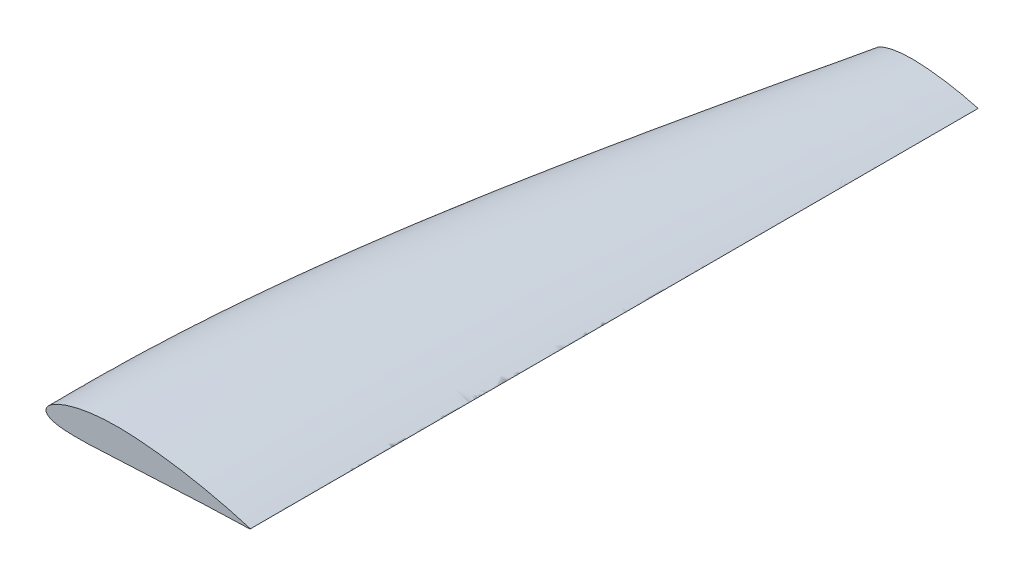
SolidWorks part; units mm, degrees
ref_plane "Front Plane" through (0, 0, 0) normal (1, 0, 0) x (0, 1, 0)
ref_plane "Top Plane" through (0, 0, 0) normal (0, 0, 1) x (0, 1, 0)
ref_plane "Right Plane" through (0, 0, 0) normal (0, 1, 0) x (-1, 0, 0)
curve "Curve1"
  spline degree 3 poles (140.0272, 0.204, 0) (139.9568, 0.2252, 0) (139.6757, 0.3101, 0) (139.0445, 0.4996, 0) (137.9962, 0.8116, 0) (136.5364, 1.24, 0) (134.6729, 1.777, 0) (132.4156, 2.4129, 0) (129.7768, 3.1359, 0) (126.7711, 3.9337, 0) (123.4152, 4.7928, 0) (119.7281, 5.6984, 0) (115.7307, 6.6363, 0) (111.4464, 7.5912, 0) (106.9, 8.5481, 0) (102.1186, 9.4924, 0) (97.1306, 10.4094, 0) (91.9664, 11.285, 0) (86.6574, 12.105, 0) (81.2364, 12.857, 0) (75.7371, 13.5278, 0) (70.1942, 14.1063, 0) (64.643, 14.582, 0) (59.1045, 14.945, 0) (53.595, 15.1934, 0) (48.1487, 15.2539, 0) (42.8195, 15.1314, 0) (37.6645, 14.8278, 0) (32.721, 14.3506, 0) (28.0244, 13.7113, 0) (23.608, 12.9241, 0) (19.5026, 12.0063, 0) (15.7359, 10.9777, 0) (12.3325, 9.8591, 0) (9.3132, 8.6734, 0) (6.6949, 7.4424, 0) (4.4906, 6.1877, 0) (2.7084, 4.928, 0) (1.3523, 3.6768, 0) (0.4223, 2.4391, 0) (-0.0704, 1.2019, 0) (-0.0774, -0.0155, 0) (0.3962, -1.1349, 0) (1.3132, -2.0898, 0) (2.6166, -2.8909, 0) (4.297, -3.5632, 0) (6.348, -4.1161, 0) (8.7591, -4.5545, 0) (11.516, -4.8827, 0) (14.6016, -5.1058, 0) (17.9973, -5.2305, 0) (21.6831, -5.2648, 0) (25.6381, -5.2189, 0) (29.8408, -5.1042, 0) (34.2692, -4.9332, 0) (38.9005, -4.7202, 0) (43.7112, -4.4799, 0) (48.6771, -4.2275, 0) (53.7919, -3.9752, 0) (59.0436, -3.7443, 0) (64.3998, -3.4808, 0) (69.8109, -3.2013, 0) (75.2301, -2.9143, 0) (80.6252, -2.6276, 0) (85.9637, -2.348, 0) (91.213, -2.0804, 0) (96.3409, -1.8293, 0) (101.3154, -1.5967, 0) (106.1052, -1.3844, 0) (110.68, -1.1929, 0) (115.0103, -1.0216, 0) (119.0681, -0.87, 0) (122.827, -0.7367, 0) (126.2621, -0.6209, 0) (129.3505, -0.521, 0) (132.0713, -0.4363, 0) (134.4061, -0.3656, 0) (136.3389, -0.3086, 0) (137.8565, -0.2644, 0) (138.948, -0.2331, 0) (139.6061, -0.2145, 0) (139.8994, -0.2061, 0) (139.9728, -0.204, 0) knots 0 0 0 0 0.000765 0.003057 0.00686 0.012149 0.018893 0.027046 0.036559 0.047372 0.059416 0.072616 0.086892 0.102153 0.118305 0.13525 0.152883 0.171093 0.18977 0.208797 0.228058 0.247433 0.266803 0.286048 0.305204 0.324202 0.342731 0.360679 0.377941 0.394414 0.410004 0.424621 0.438187 0.450631 0.461894 0.471932 0.480721 0.488263 0.494602 0.499855 0.504257 0.508229 0.5122 0.516589 0.52179 0.528018 0.535367 0.543866 0.553506 0.564253 0.57606 0.588869 0.602615 0.617228 0.632631 0.648744 0.665486 0.682768 0.700501 0.71879 0.737484 0.756321 0.775188 0.793972 0.812558 0.830833 0.848683 0.865998 0.882668 0.898589 0.913658 0.927778 0.940857 0.952809 0.963554 0.97302 0.981143 0.987868 0.993148 0.996946 0.999235 1 1 1 1
curve "Curve2"
  spline degree 3 poles (70, 0.091, 0) (68.8345, 0.4083, 0) (66.5092, 1.0413, 0) (61.851, 2.1922, 0) (56.0257, 3.4639, 0) (49.0189, 4.7174, 0) (42.0176, 5.745, 0) (35.0124, 6.4779, 0) (28.0078, 6.935, 0) (22.1603, 6.9396, 0) (17.4914, 6.6166, 0) (13.9849, 6.1912, 0) (10.4709, 5.5637, 0) (7.559, 4.8091, 0) (5.2255, 4.047, 0) (3.466, 3.3276, 0) (1.9647, 2.5495, 0) (0.6616, 1.6188, 0) (-0.4728, 0.1219, 0) (0.7517, -1.0228, 0) (2.001, -1.4722, 0) (3.489, -1.7755, 0) (5.2463, -1.9297, 0) (7.5824, -2.0389, 0) (10.5007, -2.0307, 0) (14.0015, -1.9327, 0) (17.4998, -1.7462, 0) (22.1665, -1.5279, 0) (27.9989, -1.2478, 0) (35.0002, -0.9848, 0) (41.9993, -0.6928, 0) (48.999, -0.4441, 0) (55.9993, -0.2611, 0) (61.8332, -0.1682, 0) (66.4999, -0.107, 0) (68.8333, -0.0963, 0) (70, -0.091, 0) knots 0 0 0 0 0.025305 0.050488 0.10052 0.150191 0.199587 0.24874 0.297716 0.346601 0.371103 0.395726 0.42057 0.445825 0.458702 0.47192 0.485786 0.493461 0.506863 0.516148 0.522766 0.535269 0.547551 0.559786 0.584229 0.608681 0.633151 0.657622 0.706558 0.755482 0.804406 0.85332 0.902221 0.951113 0.975557 1 1 1 1
ref_plane "Plane3" through (0, 0, -38.1) normal (0, 0, -1) x (0, 1, 0)
sketch "Sketch5" plane through (0, 0, -38.1) normal (0, 0, -1) x (0, 1, 0)
  arc A0 (-0.204, 139.9728) -> (0.204, 140.0272) centre (0.0044, 139.9669) cw
  spline S0 degree 3 poles (1884.985, 806.4833) (-22.34, 198.466) (-8.6829, 169.6209) (0.4996, 139.0445) (0.8116, 137.9962) (1.24, 136.5364) (1.777, 134.6729) (2.4129, 132.4156) (3.1359, 129.7768) (3.9337, 126.7711) (4.7928, 123.4152) (5.6984, 119.7281) (6.6363, 115.7307) (7.5912, 111.4464) (8.5481, 106.9) (9.4924, 102.1186) (10.4094, 97.1306) (11.285, 91.9664) (12.105, 86.6574) (12.857, 81.2364) (13.5278, 75.7371) (14.1063, 70.1942) (14.582, 64.643) (14.945, 59.1045) (15.1934, 53.595) (15.2539, 48.1487) (15.1314, 42.8195) (14.8278, 37.6645) (14.3506, 32.721) (13.7113, 28.0244) (12.9241, 23.608) (12.0063, 19.5026) (10.9777, 15.7359) (9.8591, 12.3325) (8.6734, 9.3132) (7.4424, 6.6949) (6.1877, 4.4906) (4.928, 2.7084) (3.6768, 1.3523) (2.4391, 0.4223) (1.2019, -0.0704) (-0.0155, -0.0774) (-1.1349, 0.3962) (-2.0898, 1.3132) (-2.8909, 2.6166) (-3.5632, 4.297) (-4.1161, 6.348) (-4.5545, 8.7591) (-4.8827, 11.516) (-5.1058, 14.6016) (-5.2305, 17.9973) (-5.2648, 21.6831) (-5.2189, 25.6381) (-5.1042, 29.8408) (-4.9332, 34.2692) (-4.7202, 38.9005) (-4.4799, 43.7112) (-4.2275, 48.6771) (-3.9752, 53.7919) (-3.7443, 59.0436) (-3.4808, 64.3998) (-3.2013, 69.8109) (-2.9143, 75.2301) (-2.6276, 80.6252) (-2.348, 85.9637) (-2.0804, 91.213) (-1.8293, 96.3409) (-1.5967, 101.3154) (-1.3844, 106.1052) (-1.1929, 110.68) (-1.0216, 115.0103) (-0.87, 119.0681) (-0.7367, 122.827) (-0.6209, 126.2621) (-0.521, 129.3505) (-0.4363, 132.0713) (-0.3656, 134.4061) (-0.3086, 136.3389) (-0.2644, 137.8565) (-0.2331, 138.948) (1.2999, 193.0557) (5.588, 246.7199) (-1986.0508, 357.0454) knots -0.325451 -0.325451 -0.325451 -0.325451 0.000765 0.003057 0.00686 0.012149 0.018893 0.027046 0.036559 0.047372 0.059416 0.072616 0.086892 0.102153 0.118305 0.13525 0.152883 0.171093 0.18977 0.208797 0.228058 0.247433 0.266803 0.286048 0.305204 0.324202 0.342731 0.360679 0.377941 0.394414 0.410004 0.424621 0.438187 0.450631 0.461894 0.471932 0.480721 0.488263 0.494602 0.499855 0.504257 0.508229 0.5122 0.516589 0.52179 0.528018 0.535367 0.543866 0.553506 0.564253 0.57606 0.588869 0.602615 0.617228 0.632631 0.648744 0.665486 0.682768 0.700501 0.71879 0.737484 0.756321 0.775188 0.793972 0.812558 0.830833 0.848683 0.865998 0.882668 0.898589 0.913658 0.927778 0.940857 0.952809 0.963554 0.97302 0.981143 0.987868 0.993148 0.996946 0.999235 1.556579 1.556579 1.556579 1.556579 only from (0.204, 140.0272) to (-0.204, 139.9728) construction
  spline S1 degree 3 poles (0.204, 140.0272) (0.2252, 139.9568) (0.3101, 139.6757) (0.4996, 139.0445) (0.8116, 137.9962) (1.24, 136.5364) (1.777, 134.6729) (2.4129, 132.4156) (3.1359, 129.7768) (3.9337, 126.7711) (4.7928, 123.4152) (5.6984, 119.7281) (6.6363, 115.7307) (7.5912, 111.4464) (8.5481, 106.9) (9.4924, 102.1186) (10.4094, 97.1306) (11.285, 91.9664) (12.105, 86.6574) (12.857, 81.2364) (13.5278, 75.7371) (14.1063, 70.1942) (14.582, 64.643) (14.945, 59.1045) (15.1934, 53.595) (15.2539, 48.1487) (15.1314, 42.8195) (14.8278, 37.6645) (14.3506, 32.721) (13.7113, 28.0244) (12.9241, 23.608) (12.0063, 19.5026) (10.9777, 15.7359) (9.8591, 12.3325) (8.6734, 9.3132) (7.4424, 6.6949) (6.1877, 4.4906) (4.928, 2.7084) (3.6768, 1.3523) (2.4391, 0.4223) (1.2019, -0.0704) (-0.0155, -0.0774) (-1.1349, 0.3962) (-2.0898, 1.3132) (-2.8909, 2.6166) (-3.5632, 4.297) (-4.1161, 6.348) (-4.5545, 8.7591) (-4.8827, 11.516) (-5.1058, 14.6016) (-5.2305, 17.9973) (-5.2648, 21.6831) (-5.2189, 25.6381) (-5.1042, 29.8408) (-4.9332, 34.2692) (-4.7202, 38.9005) (-4.4799, 43.7112) (-4.2275, 48.6771) (-3.9752, 53.7919) (-3.7443, 59.0436) (-3.4808, 64.3998) (-3.2013, 69.8109) (-2.9143, 75.2301) (-2.6276, 80.6252) (-2.348, 85.9637) (-2.0804, 91.213) (-1.8293, 96.3409) (-1.5967, 101.3154) (-1.3844, 106.1052) (-1.1929, 110.68) (-1.0216, 115.0103) (-0.87, 119.0681) (-0.7367, 122.827) (-0.6209, 126.2621) (-0.521, 129.3505) (-0.4363, 132.0713) (-0.3656, 134.4061) (-0.3086, 136.3389) (-0.2644, 137.8565) (-0.2331, 138.948) (-0.2145, 139.6061) (-0.2061, 139.8994) (-0.204, 139.9728) knots 0 0 0 0 0.000765 0.003057 0.00686 0.012149 0.018893 0.027046 0.036559 0.047372 0.059416 0.072616 0.086892 0.102153 0.118305 0.13525 0.152883 0.171093 0.18977 0.208797 0.228058 0.247433 0.266803 0.286048 0.305204 0.324202 0.342731 0.360679 0.377941 0.394414 0.410004 0.424621 0.438187 0.450631 0.461894 0.471932 0.480721 0.488263 0.494602 0.499855 0.504257 0.508229 0.5122 0.516589 0.52179 0.528018 0.535367 0.543866 0.553506 0.564253 0.57606 0.588869 0.602615 0.617228 0.632631 0.648744 0.665486 0.682768 0.700501 0.71879 0.737484 0.756321 0.775188 0.793972 0.812558 0.830833 0.848683 0.865998 0.882668 0.898589 0.913658 0.927778 0.940857 0.952809 0.963554 0.97302 0.981143 0.987868 0.993148 0.996946 0.999235 1 1 1 1
sketch "Sketch3" plane through (0, 0, 0) normal (0, 0, 1) x (0, 1, 0)
  arc A0 (-0.204, -139.9728) -> (0.204, -140.0272) centre (0.0044, -139.9669) ccw
  spline S0 degree 3 poles (2838.3113, -1108.2184) (-26.355, -206.7185) (-9.9859, -173.9596) (0.4996, -139.0445) (0.8116, -137.9962) (1.24, -136.5364) (1.777, -134.6729) (2.4129, -132.4156) (3.1359, -129.7768) (3.9337, -126.7711) (4.7928, -123.4152) (5.6984, -119.7281) (6.6363, -115.7307) (7.5912, -111.4464) (8.5481, -106.9) (9.4924, -102.1186) (10.4094, -97.1306) (11.285, -91.9664) (12.105, -86.6574) (12.857, -81.2364) (13.5278, -75.7371) (14.1063, -70.1942) (14.582, -64.643) (14.945, -59.1045) (15.1934, -53.595) (15.2539, -48.1487) (15.1314, -42.8195) (14.8278, -37.6645) (14.3506, -32.721) (13.7113, -28.0244) (12.9241, -23.608) (12.0063, -19.5026) (10.9777, -15.7359) (9.8591, -12.3325) (8.6734, -9.3132) (7.4424, -6.6949) (6.1877, -4.4906) (4.928, -2.7084) (3.6768, -1.3523) (2.4391, -0.4223) (1.2019, 0.0704) (-0.0155, 0.0774) (-1.1349, -0.3962) (-2.0898, -1.3132) (-2.8909, -2.6166) (-3.5632, -4.297) (-4.1161, -6.348) (-4.5545, -8.7591) (-4.8827, -11.516) (-5.1058, -14.6016) (-5.2305, -17.9973) (-5.2648, -21.6831) (-5.2189, -25.6381) (-5.1042, -29.8408) (-4.9332, -34.2692) (-4.7202, -38.9005) (-4.4799, -43.7112) (-4.2275, -48.6771) (-3.9752, -53.7919) (-3.7443, -59.0436) (-3.4808, -64.3998) (-3.2013, -69.8109) (-2.9143, -75.2301) (-2.6276, -80.6252) (-2.348, -85.9637) (-2.0804, -91.213) (-1.8293, -96.3409) (-1.5967, -101.3154) (-1.3844, -106.1052) (-1.1929, -110.68) (-1.0216, -115.0103) (-0.87, -119.0681) (-0.7367, -122.827) (-0.6209, -126.2621) (-0.521, -129.3505) (-0.4363, -132.0713) (-0.3656, -134.4061) (-0.3086, -136.3389) (-0.2644, -137.8565) (-0.2331, -138.948) (1.5198, -200.8184) (6.8844, -262.2209) (-2984.6684, -408.8116) knots -0.372605 -0.372605 -0.372605 -0.372605 0.000765 0.003057 0.00686 0.012149 0.018893 0.027046 0.036559 0.047372 0.059416 0.072616 0.086892 0.102153 0.118305 0.13525 0.152883 0.171093 0.18977 0.208797 0.228058 0.247433 0.266803 0.286048 0.305204 0.324202 0.342731 0.360679 0.377941 0.394414 0.410004 0.424621 0.438187 0.450631 0.461894 0.471932 0.480721 0.488263 0.494602 0.499855 0.504257 0.508229 0.5122 0.516589 0.52179 0.528018 0.535367 0.543866 0.553506 0.564253 0.57606 0.588869 0.602615 0.617228 0.632631 0.648744 0.665486 0.682768 0.700501 0.71879 0.737484 0.756321 0.775188 0.793972 0.812558 0.830833 0.848683 0.865998 0.882668 0.898589 0.913658 0.927778 0.940857 0.952809 0.963554 0.97302 0.981143 0.987868 0.993148 0.996946 0.999235 1.637413 1.637413 1.637413 1.637413 only from (0.204, -140.0272) to (-0.204, -139.9728) construction
  spline S1 degree 3 poles (0.204, -140.0272) (0.2252, -139.9568) (0.3101, -139.6757) (0.4996, -139.0445) (0.8116, -137.9962) (1.24, -136.5364) (1.777, -134.6729) (2.4129, -132.4156) (3.1359, -129.7768) (3.9337, -126.7711) (4.7928, -123.4152) (5.6984, -119.7281) (6.6363, -115.7307) (7.5912, -111.4464) (8.5481, -106.9) (9.4924, -102.1186) (10.4094, -97.1306) (11.285, -91.9664) (12.105, -86.6574) (12.857, -81.2364) (13.5278, -75.7371) (14.1063, -70.1942) (14.582, -64.643) (14.945, -59.1045) (15.1934, -53.595) (15.2539, -48.1487) (15.1314, -42.8195) (14.8278, -37.6645) (14.3506, -32.721) (13.7113, -28.0244) (12.9241, -23.608) (12.0063, -19.5026) (10.9777, -15.7359) (9.8591, -12.3325) (8.6734, -9.3132) (7.4424, -6.6949) (6.1877, -4.4906) (4.928, -2.7084) (3.6768, -1.3523) (2.4391, -0.4223) (1.2019, 0.0704) (-0.0155, 0.0774) (-1.1349, -0.3962) (-2.0898, -1.3132) (-2.8909, -2.6166) (-3.5632, -4.297) (-4.1161, -6.348) (-4.5545, -8.7591) (-4.8827, -11.516) (-5.1058, -14.6016) (-5.2305, -17.9973) (-5.2648, -21.6831) (-5.2189, -25.6381) (-5.1042, -29.8408) (-4.9332, -34.2692) (-4.7202, -38.9005) (-4.4799, -43.7112) (-4.2275, -48.6771) (-3.9752, -53.7919) (-3.7443, -59.0436) (-3.4808, -64.3998) (-3.2013, -69.8109) (-2.9143, -75.2301) (-2.6276, -80.6252) (-2.348, -85.9637) (-2.0804, -91.213) (-1.8293, -96.3409) (-1.5967, -101.3154) (-1.3844, -106.1052) (-1.1929, -110.68) (-1.0216, -115.0103) (-0.87, -119.0681) (-0.7367, -122.827) (-0.6209, -126.2621) (-0.521, -129.3505) (-0.4363, -132.0713) (-0.3656, -134.4061) (-0.3086, -136.3389) (-0.2644, -137.8565) (-0.2331, -138.948) (-0.2145, -139.6061) (-0.2061, -139.8994) (-0.204, -139.9728) knots 0 0 0 0 0.000765 0.003057 0.00686 0.012149 0.018893 0.027046 0.036559 0.047372 0.059416 0.072616 0.086892 0.102153 0.118305 0.13525 0.152883 0.171093 0.18977 0.208797 0.228058 0.247433 0.266803 0.286048 0.305204 0.324202 0.342731 0.360679 0.377941 0.394414 0.410004 0.424621 0.438187 0.450631 0.461894 0.471932 0.480721 0.488263 0.494602 0.499855 0.504257 0.508229 0.5122 0.516589 0.52179 0.528018 0.535367 0.543866 0.553506 0.564253 0.57606 0.588869 0.602615 0.617228 0.632631 0.648744 0.665486 0.682768 0.700501 0.71879 0.737484 0.756321 0.775188 0.793972 0.812558 0.830833 0.848683 0.865998 0.882668 0.898589 0.913658 0.927778 0.940857 0.952809 0.963554 0.97302 0.981143 0.987868 0.993148 0.996946 0.999235 1 1 1 1
ref_plane "Plane2" through (0, 0, -500) normal (0, 0, 1) x (0, 1, 0)
sketch "Sketch4" plane through (0, 0, -500) normal (0, 0, 1) x (0, 1, 0)
  arc A1 (-0.0866, -139.9917) -> (0.0954, -139.9917) centre (0.0044, -139.9669) ccw
  spline S2 degree 3 poles (0.0954, -139.9917) (0.4127, -138.8262) (1.0457, -136.5009) (2.1966, -131.8427) (3.4683, -126.0174) (4.7218, -119.0106) (5.7494, -112.0093) (6.4823, -105.0041) (6.9394, -97.9995) (6.944, -92.152) (6.621, -87.4831) (6.1956, -83.9766) (5.5681, -80.4626) (4.8135, -77.5507) (4.0514, -75.2172) (3.332, -73.4577) (2.5539, -71.9564) (1.6232, -70.6533) (0.1263, -69.5189) (-1.0184, -70.7433) (-1.4678, -71.9927) (-1.7711, -73.4807) (-1.9253, -75.2379) (-2.0345, -77.5741) (-2.0263, -80.4924) (-1.9283, -83.9932) (-1.7418, -87.4915) (-1.5235, -92.1582) (-1.2434, -97.9906) (-0.9804, -104.9919) (-0.6884, -111.991) (-0.4397, -118.9907) (-0.2567, -125.991) (-0.1638, -131.8248) (-0.1026, -136.4916) (-0.0919, -138.825) (-0.0866, -139.9917) knots 0 0 0 0 0.025305 0.050488 0.10052 0.150191 0.199587 0.24874 0.297716 0.346601 0.371103 0.395726 0.42057 0.445825 0.458702 0.47192 0.485786 0.493461 0.506863 0.516148 0.522766 0.535269 0.547551 0.559786 0.584229 0.608681 0.633151 0.657622 0.706558 0.755482 0.804406 0.85332 0.902221 0.951113 0.975557 1 1 1 1
loft "Loft1" add profiles "Sketch4", "Sketch5", "Sketch3" connector at (139.9917, -0.0866, -500) connector at (139.9728, -0.204, -38.1) connector at (139.9728, -0.204, 0)
